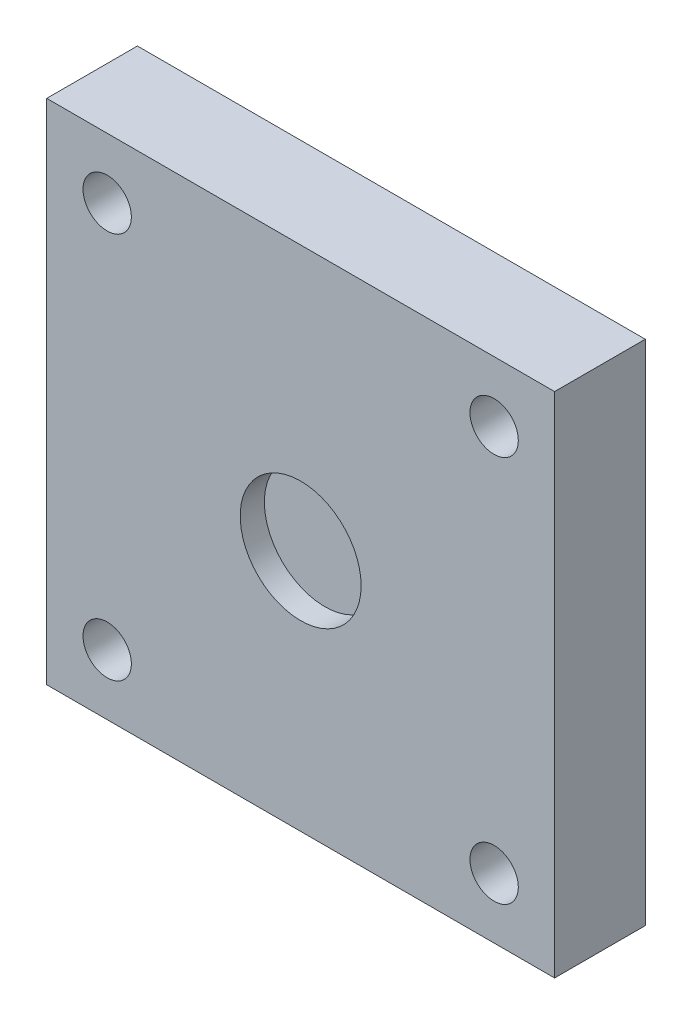
SolidWorks part; units mm, degrees
ref_plane "Front Plane" through (0, 0, 0) normal (0, 0, 1) x (1, 0, 0)
ref_plane "Top Plane" through (0, 0, 0) normal (0, 1, 0) x (1, 0, 0)
ref_plane "Right Plane" through (0, 0, 0) normal (1, 0, 0) x (0, 0, -1)
sketch "Sketch2" plane through (0, 0, 0) normal (0, 0, 1) x (1, 0, 0)
  line L0 (-3.9478, 33.5) -> (38.0522, -8.5) construction
  line L1 (-3.9478, 33.5) -> (38.0522, 33.5)
  line L2 (-3.9478, 33.5) -> (-3.9478, -8.5)
  line L3 (-3.9478, -8.5) -> (38.0522, -8.5)
  line L4 (38.0522, 33.5) -> (38.0522, -8.5)
  line L5 (38.0522, 33.5) -> (-3.9478, -8.5) construction
  circle A8 centre (1.0522, 28.5) radius 2
  circle A12 centre (1.0522, -3.5) radius 2
  circle A13 centre (33.0522, -3.5) radius 2
  circle A14 centre (33.0522, 28.5) radius 2
  point P32 (17.0522, 12.5)
  dimension "D3" = 42
  dimension "D4" = 45.2548
  dimension "D1" = 42
  dimension "D2" = 42
  dimension "D5" = 45.2548
extrude "Boss-Extrude3" add sketch "Sketch2" along normal blind 5.5 contours A14 | A8 | L2 L1 L4 L3 | A12 | A13 region at (1.0522, 28.5, 0) region at (33.0522, 28.5, 0)
sketch "Sketch5" plane through (0, 0, 5.5) normal (0, 0, 1) x (1, 0, 0)
  line L1 (-3.9478, 33.5) -> (38.0522, 33.5)
  line L2 (-3.9478, 33.5) -> (-3.9478, -8.5)
  line L3 (-3.9478, -8.5) -> (38.0522, -8.5)
  line L4 (38.0522, 33.5) -> (38.0522, -8.5)
  circle A0 centre (1.0522, 28.5) radius 2
  circle A1 centre (33.0522, 28.5) radius 2
  circle A2 centre (1.0522, -3.5) radius 2
  circle A3 centre (33.0522, -3.5) radius 2
  circle A4 centre (17.0522, 11.5921) radius 5
  circle M10 centre (33.0522, 28.5) radius 2
  circle M11 centre (1.0522, 28.5) radius 2
  circle M12 centre (1.0522, -3.5) radius 2
  circle M13 centre (33.0522, -3.5) radius 2
extrude "Boss-Extrude5" add sketch "Sketch5" along normal blind 2 contours M11 | A4 | M10 | M13 | M12 | L2 L1 L4 L3 region at (1.0522, 28.5, 5.5) region at (33.0522, 28.5, 5.5) region at (1.0522, -3.5, 5.5) region at (33.0522, -3.5, 5.5) region at (17.0522, 11.5921, 5.5)
